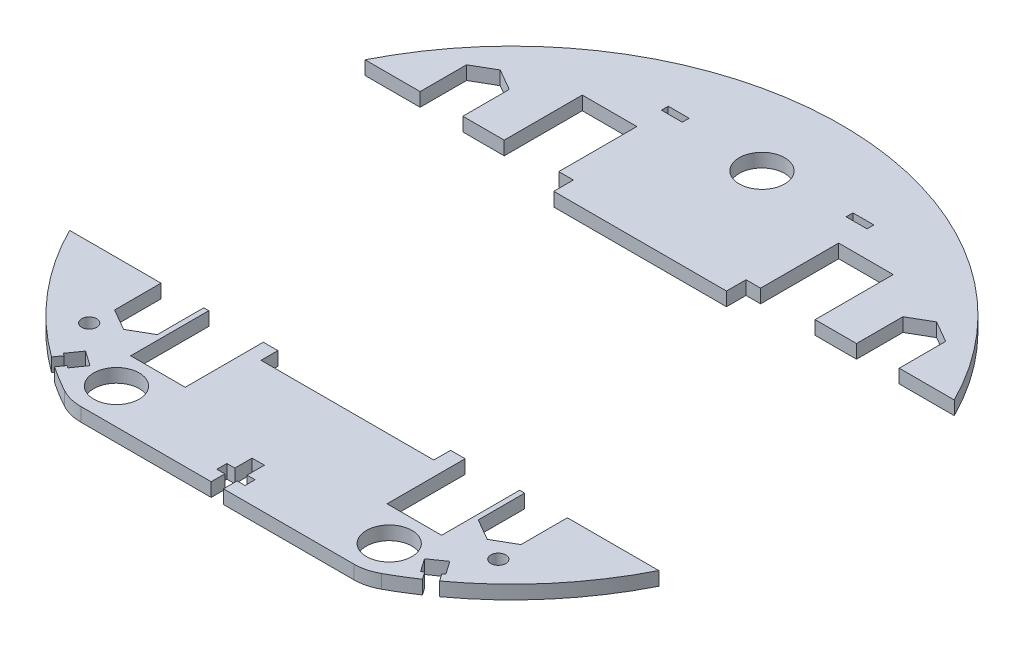
SolidWorks part; units mm, degrees
ref_plane "Front Plane" through (0, 0, 0) normal (0, 0, 1) x (1, 0, 0)
ref_plane "Top Plane" through (0, 0, 0) normal (0, 1, 0) x (1, 0, 0)
ref_plane "Right Plane" through (0, 0, 0) normal (1, 0, 0) x (0, 0, -1)
sketch "Sketch1" plane through (0, 0, 0) normal (0, 1, 0) x (1, 0, 0)
  line L0 (-30.03, -64.8129) -> (30.03, -64.8129)
  line L1 (0, -85) -> (0, 0) construction
  line L2 (0, -85) -> (32.4891, -64.8129) construction
  arc A0 (34.8348, -63.5829) -> (-34.8348, -63.5829) centre (0, 0) ccw
  circle A1 centre (0, -85) radius 38.25 construction
  arc A2 (30.03, -64.8129) -> (34.8348, -63.5829) centre (30.03, -54.8129) ccw
  arc A3 (-30.03, -64.8129) -> (-34.8348, -63.5829) centre (-30.03, -54.8129) cw
  dimension "D1" = 145
  dimension "D2" = 76.5
  dimension "D4" = 10
  dimension "D3" = 85
extrude "Boss-Extrude1" add sketch "Sketch1" along normal blind 3
sketch "Sketch2" plane through (0, 3, 0) normal (0, 1, 0) x (1, 0, 0)
  line L0 (18, -36.2) -> (-18, -36.2) construction
  line L1 (-34.2, -49.6757) -> (-22.2, -49.6757)
  line L2 (-34.2, -49.6757) -> (-34.2, 49.6757)
  line L3 (-34.2, 49.6757) -> (-22.2, 49.6757)
  line L4 (-22.2, -49.6757) -> (-22.2, -32.5)
  line L5 (-19, -32.5) -> (-22.2, -32.5) construction
  line L6 (-22.2, -49.6757) -> (-22.2, -32.5)
  line L7 (-19, -32.5) -> (-22.2, -32.5)
  line L8 (19, 28.2) -> (-19, 28.2) construction
  line L9 (18, -36.2) -> (-18, -36.2)
  line L10 (-19, 32.5) -> (-22.2, 32.5) construction
  line L11 (-19, 32.5) -> (-22.2, 32.5)
  line L12 (19, 28.2) -> (-19, 28.2)
  line L13 (-19, -32.5) -> (-19, -36.2)
  line L14 (-19, -36.2) -> (-18, -36.2)
  line L15 (-19, 32.5) -> (-19, 28.2)
  line L16 (-22.2, 32.5) -> (-22.2, 49.6757)
  line L17 (0, 0) -> (0, -64.8129) construction
  line L18 (-30.03, -64.8129) -> (30.03, -64.8129) construction
  line L19 (22.2, 32.5) -> (22.2, 49.6757)
  line L20 (19, 32.5) -> (19, 28.2)
  line L21 (19, -36.2) -> (18, -36.2)
  line L22 (19, -32.5) -> (19, -36.2)
  line L23 (19, 32.5) -> (22.2, 32.5)
  line L24 (19, -32.5) -> (22.2, -32.5)
  line L25 (22.2, -49.6757) -> (22.2, -32.5)
  line L26 (22.2, -49.6757) -> (22.2, -32.5)
  line L27 (34.2, 49.6757) -> (22.2, 49.6757)
  line L28 (34.2, -49.6757) -> (34.2, 49.6757)
  line L29 (34.2, -49.6757) -> (22.2, -49.6757)
extrude "Cut-Extrude1" cut sketch "Sketch2" against normal through all contours L29 L28 L27 L19 L23 L20 L12 L15 L11 L16 L3 L2 L1 L4 L7 L13 L14 L9 L21 L22 L24 L25 region at (0, 3, 1.8654)
sketch "Sketch3" plane through (0, 3, 0) normal (0, 1, 0) x (1, 0, 0)
  line L0 (-34.2, 32.5) -> (-34.2, -32.5)
  line L1 (-72.5, -32.5) -> (-34.2, -32.5)
  line L2 (-72.5, -32.5) -> (-72.5, 32.5)
  line L3 (-72.5, 32.5) -> (-34.2, 32.5)
  line L4 (72.5, -32.5) -> (72.5, 32.5)
  line L5 (-72.5, -32.5) -> (72.5, 32.5) construction
  line L6 (-72.5, 32.5) -> (72.5, -32.5) construction
  line L7 (-34.2, -49.6757) -> (-34.2, 49.6757) construction
  line L8 (34.2, 32.5) -> (34.2, -32.5)
  line L9 (34.2, -49.6757) -> (34.2, 49.6757) construction
  line L10 (34.2, 32.5) -> (72.5, 32.5)
  line L11 (34.2, -32.5) -> (72.5, -32.5)
  arc A0 (34.8348, -63.5829) -> (-34.8348, -63.5829) centre (0, 0) ccw construction
  point P0 (0, 0)
  dimension "D1" = 65
extrude "Cut-Extrude2" cut sketch "Sketch3" against normal through all
sketch "Sketch4" plane through (0, 3, 0) normal (0, 1, 0) x (1, 0, 0)
  line L0 (0, 0) -> (0, -20.7985) construction
  circle A0 centre (30, -57) radius 5
  circle A4 centre (-30, -57) radius 5
  dimension "D3" = 10
  dimension "D1" = 57
  dimension "D2" = 30
extrude "Cut-Extrude3" cut sketch "Sketch4" against normal through all
sketch "Sketch5" plane through (0, 3, 0) normal (0, 1, 0) x (1, 0, 0)
  line L0 (-52.7, 37.2865) -> (-52.7, 32.5)
  line L2 (-34.2, 32.5) -> (-64.8074, 32.5) construction
  line L3 (-52.7, 32.5) -> (-43.3, 32.5)
  line L4 (-43.3, 32.5) -> (-43.3, 37.2865)
  line L6 (-44.7, -37.2865) -> (-44.7, -32.5)
  line L7 (-64.8074, -32.5) -> (-34.2, -32.5) construction
  line L8 (0, 0) -> (0, -64.8129) construction
  line L9 (-30.03, -64.8129) -> (30.03, -64.8129) construction
  line L16 (-35.3, -37.2865) -> (-35.3, -32.5)
  line L17 (-43.3, 42.7135) -> (-48, 45.4271)
  line L18 (-48, 45.4271) -> (-52.7, 42.7135)
  line L19 (-52.7, 42.7135) -> (-52.7, 37.2865)
  line L20 (-52.7, 37.2865) -> (-48, 34.5729) construction
  line L21 (-48, 34.5729) -> (-43.3, 37.2865) construction
  line L22 (-43.3, 37.2865) -> (-43.3, 42.7135)
  line L23 (-40, -34.5729) -> (-44.7, -37.2865) construction
  line L24 (-44.7, -37.2865) -> (-44.7, -42.7135)
  line L25 (-44.7, -42.7135) -> (-40, -45.4271)
  line L26 (-40, -45.4271) -> (-35.3, -42.7135)
  line L27 (-35.3, -42.7135) -> (-35.3, -37.2865)
  line L28 (-35.3, -37.2865) -> (-40, -34.5729) construction
  line L30 (-35.3, -32.5) -> (-44.7, -32.5)
  line L31 (35.3, -37.2865) -> (40, -34.5729) construction
  line L32 (40, -34.5729) -> (44.7, -37.2865) construction
  line L33 (48, 34.5729) -> (43.3, 37.2865) construction
  line L34 (52.7, 37.2865) -> (48, 34.5729) construction
  line L35 (35.3, -32.5) -> (44.7, -32.5)
  line L36 (35.3, -42.7135) -> (35.3, -37.2865)
  line L37 (40, -45.4271) -> (35.3, -42.7135)
  line L38 (44.7, -42.7135) -> (40, -45.4271)
  line L39 (44.7, -37.2865) -> (44.7, -42.7135)
  line L40 (43.3, 37.2865) -> (43.3, 42.7135)
  line L41 (52.7, 42.7135) -> (52.7, 37.2865)
  line L42 (48, 45.4271) -> (52.7, 42.7135)
  line L43 (43.3, 42.7135) -> (48, 45.4271)
  line L44 (35.3, -37.2865) -> (35.3, -32.5)
  line L45 (44.7, -37.2865) -> (44.7, -32.5)
  line L46 (43.3, 32.5) -> (43.3, 37.2865)
  line L47 (52.7, 32.5) -> (43.3, 32.5)
  line L48 (52.7, 37.2865) -> (52.7, 32.5)
  circle A2 centre (-48, 40) radius 4.7 construction
  circle A3 centre (-40, -40) radius 4.7 construction
  circle A4 centre (40, -40) radius 4.7 construction
  circle A5 centre (48, 40) radius 4.7 construction
  dimension "D1" = 9.4
  dimension "D2" = 48
  dimension "D3" = 40
  dimension "D4" = 40
  dimension "D5" = 40
  dimension "D6" = 9.4
extrude "Cut-Extrude4" cut sketch "Sketch5" against normal through all
sketch "Sketch6" plane through (0, 3, 0) normal (0, 1, 0) x (1, 0, 0)
  line L4 (-18.02, 55.5) -> (-18.02, 57)
  line L5 (-22.62, 55.5) -> (-18.02, 55.5)
  line L6 (-22.62, 57) -> (-22.62, 55.5)
  line L7 (-18.02, 57) -> (-22.62, 57)
  line L8 (-18.02, 55.5) -> (-18.02, 57)
  line L9 (-22.62, 55.5) -> (-18.02, 55.5)
  line L10 (-22.62, 57) -> (-22.62, 55.5)
  line L11 (-18.02, 57) -> (-22.62, 57)
  line L12 (22.62, 57) -> (18.02, 57)
  line L13 (18.02, 57) -> (18.02, 55.5)
  line L14 (18.02, 55.5) -> (22.62, 55.5)
  line L15 (22.62, 55.5) -> (22.62, 57)
  line L16 (22.62, 57) -> (18.02, 57)
  line L17 (18.02, 57) -> (18.02, 55.5)
  line L18 (18.02, 55.5) -> (22.62, 55.5)
  line L19 (22.62, 55.5) -> (22.62, 57)
  dimension "D1" = 0
  dimension "D2" = 0
extrude "Cut-Extrude5" cut sketch "Sketch6" against normal through all
sketch "Sketch7" plane through (0, 3, 0) normal (0, 1, 0) x (1, 0, 0)
  line L0 (0, 0) -> (0, 55) construction
  circle A0 centre (0, 55) radius 5
  dimension "D1" = 10
  dimension "D2" = 55
extrude "Cut-Extrude6" cut sketch "Sketch7" against normal through all
sketch "Sketch8" plane through (0, 3, 0) normal (0, 1, 0) x (1, 0, 0)
  line L0 (-1.35, -64.8129) -> (-1.35, -61.8129)
  line L1 (-30.03, -64.8129) -> (30.03, -64.8129) construction
  line L2 (-1.35, -61.8129) -> (-3.1, -61.8129)
  line L3 (-3.1, -61.8129) -> (-3.1, -59.6129)
  line L4 (-3.1, -59.6129) -> (-1.35, -59.6129)
  line L5 (-1.35, -59.6129) -> (-1.35, -55.8129)
  line L6 (-1.35, -55.8129) -> (1.35, -55.8129)
  line L7 (1.35, -55.8129) -> (1.35, -59.6129)
  line L8 (1.35, -59.6129) -> (3.1, -59.6129)
  line L9 (3.1, -59.6129) -> (3.1, -61.8129)
  line L10 (3.1, -61.8129) -> (1.35, -61.8129)
  line L11 (1.35, -61.8129) -> (1.35, -64.8129)
  line L12 (-1.35, -64.8129) -> (1.35, -64.8129)
  line L13 (-30.03, -64.8129) -> (30.03, -64.8129) construction
  point P7 (-6.9711, -64.8129)
  point P15 (0, 0)
  point P18 (0, -64.8129)
  point P19 (0, -64.8129)
  point P20 (13.233, -54.599)
  point P21 (5.2485, -59.4019)
  dimension "D1" = 2.7
  dimension "D2" = 2.2
  dimension "D3" = 6.2
  dimension "D5" = 9
extrude "Cut-Extrude7" cut sketch "Sketch8" against normal through all
sketch "Sketch9" plane through (0, 3, 0) normal (0, 1, 0) x (1, 0, 0)
  line L0 (0, 0) -> (0, -27.4582) construction
  circle A0 centre (45, -48) radius 1.65
  circle A1 centre (-45, -48) radius 1.65
  dimension "D3" = 3.3
  dimension "D1" = 45
  dimension "D2" = 48
extrude "Cut-Extrude8" cut sketch "Sketch9" against normal through all
sketch "Sketch10" plane through (0, 3, 0) normal (0, 1, 0) x (1, 0, 0)
  line L0 (0, 0) -> (0, -36.2) construction
  line L1 (-19, -36.2) -> (19, -36.2) construction
  line L2 (0, 0) -> (41.5843, -59.3885) construction
  line L3 (36.7913, -56.0303) -> (40.0679, -53.736)
  line L4 (36.7913, -56.0303) -> (38.7988, -58.8974)
  line L5 (40.0679, -53.736) -> (42.0754, -56.6031)
  line L6 (38.7988, -58.8974) -> (39.3313, -58.5245)
  line L7 (39.3313, -58.5245) -> (40.4784, -60.1629)
  line L8 (40.4784, -60.1629) -> (42.6901, -58.6142)
  line L9 (42.6901, -58.6142) -> (41.543, -56.9759)
  line L10 (41.543, -56.9759) -> (42.0754, -56.6031)
  line L11 (-41.543, -56.9759) -> (-42.0754, -56.6031)
  line L12 (-42.6901, -58.6142) -> (-41.543, -56.9759)
  line L13 (-40.4784, -60.1629) -> (-42.6901, -58.6142)
  line L14 (-39.3313, -58.5245) -> (-40.4784, -60.1629)
  line L15 (-38.7988, -58.8974) -> (-39.3313, -58.5245)
  line L16 (-40.0679, -53.736) -> (-42.0754, -56.6031)
  line L17 (-36.7913, -56.0303) -> (-38.7988, -58.8974)
  line L18 (-36.7913, -56.0303) -> (-40.0679, -53.736)
  arc A0 (34.8348, -63.5829) -> (64.8074, -32.5) centre (0, 0) ccw construction
  point P5 (38.4296, -54.8832)
  point P18 (41.5843, -59.3885)
  point P19 (42.3669, -58.8405)
  dimension "D1" = 35
  dimension "D2" = 4
  dimension "D3" = 3.5
  dimension "D4" = 2.7
  dimension "D5" = 2
extrude "Cut-Extrude9" cut sketch "Sketch10" against normal through all
equation "\"smallPulleyTeeth\"= 30"
equation "\"largePulleyTeeth\"= 30"
equation "\"eighthThick\"= 3.0mm"
equation "\"sixteenthThick\" = 1.7mm"
equation "\"quarterThick\"=6.0mm"
equation "\"OD\" = 145mm"
equation "\"puckAngle\" = 60.5deg"
equation "\"puckDiam\" = 76.5mm"
equation "\"axlePress\" = 5.9mm"
equation "\"press\" = 0.2mm"
equation "\"wheelClear\" = 0.3mm"
equation "\"10-32clear\" = 4.8mm"
equation "\"6-32clear\" = 3.3mm"
equation "\"8-32clear\" = 4.0mm"
equation "\"4-40clear\" = 3.0mm"
equation "\"wheelHeight\" = 22mm"
equation "\"wheelWell\" = 65mm"
equation "\"D1@Sketch1\"=\"OD\""
equation "\"D1@Boss-Extrude1\"=\"eighthThick\""
equation "\"D2@Sketch1\"=\"puckDiam\""
equation "\"D1@Sketch3\"=\"wheelWell\""
equation "\"puckDist\" = 85mm"
equation "\"scoopFillet\" = 5mm"
equation "\"10-32tap\" = 4.45mm"
equation "\"ledSmall\" = 3.1mm"
equation "\"ledLarge\" = 4.2mm"
equation "\"ledLength\" = 4.2mm"
equation "\"D3@Sketch1\"=\"puckDist\""
equation "\"4-40close\" = 2.7mm"
equation "\"4-40nutThick\" = 2.2mm"
equation "\"4-40nutWidth\" = 6.2mm"
equation "\"D1@Sketch8\"=\"4-40close\""
equation "\"D3@Sketch8\"=\"4-40nutWidth\""
equation "\"D3@Sketch9\"=\"6-32clear\""
equation "\"4-40insertHeight\" = 3.5mm"
equation "\"4-40insert\" = 4mm"
equation "\"D2@Sketch10\"=\"4-40insert\""
equation "\"D3@Sketch10\"=\"4-40insertHeight\""
equation "\"D4@Sketch10\"=\"4-40close\""
